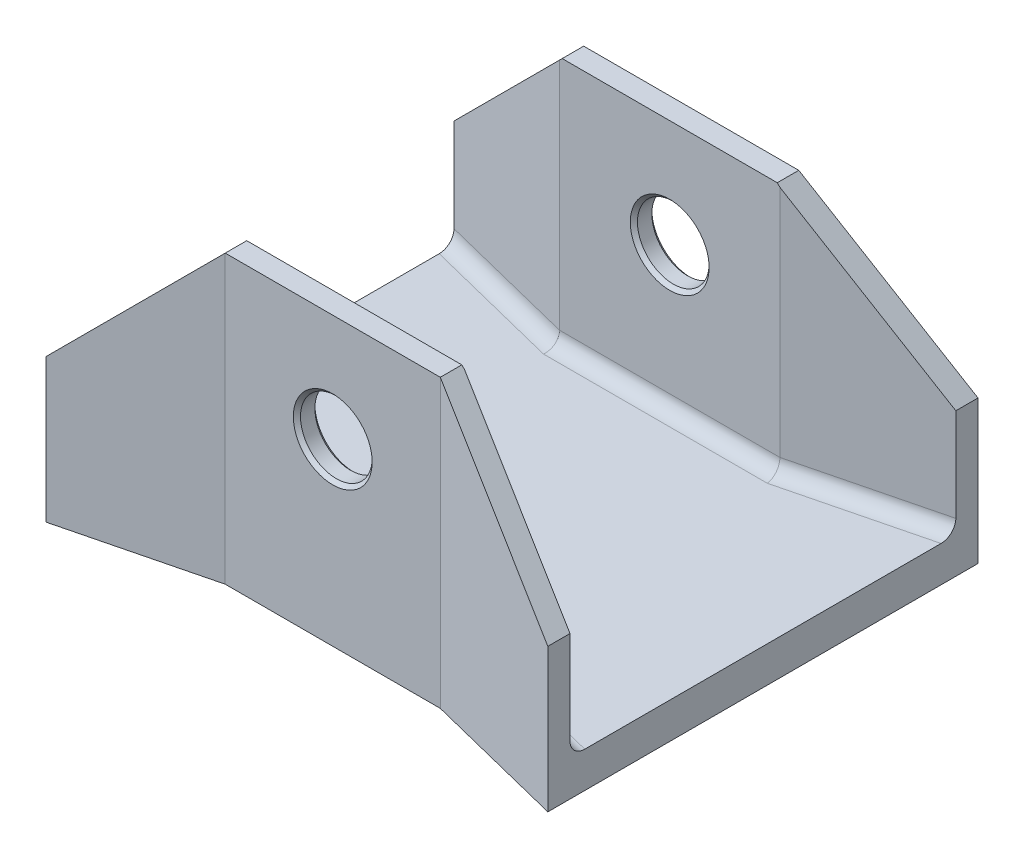
SolidWorks part; units mm, degrees
ref_plane "Front Plane" through (0, 0, 0) normal (0, 0, 1) x (1, 0, 0)
ref_plane "Top Plane" through (0, 0, 0) normal (0, 1, 0) x (1, 0, 0)
ref_plane "Right Plane" through (0, 0, 0) normal (1, 0, 0) x (0, 0, -1)
sketch "Sketch1" plane through (0, 0, 0) normal (0, 1, 0) x (1, 0, 0)
  line L0 (-566.7955, 0) -> (27772.9795, 0) construction
  line L1 (-35, -30) -> (-35, 30)
  line L2 (-35, 30) -> (-15, 25)
  line L3 (-15, 25) -> (15, 25)
  line L4 (0, -566.7955) -> (0, 27772.9795) construction
  line L5 (35, -30) -> (35, 30)
  line L6 (35, 30) -> (15, 25)
  line L7 (35, -30) -> (15, -25)
  line L8 (-15, -25) -> (15, -25)
  line L9 (-35, -30) -> (-15, -25)
  point P1 (0, -25)
  point P6 (0, 10.6994)
  point P10 (0, 25)
  point P15 (35, 0)
  point P17 (-35, 0)
  dimension "D1" = 15
  dimension "D2" = 35
  dimension "D3" = 30
  dimension "D4" = 25
extrude "Boss-Extrude1" add sketch "Sketch1" along normal blind 40
sketch "Sketch2" plane through (0, 40, 0) normal (0, 1, 0) x (1, 0, 0)
  line L0 (-15.3693, 22) -> (-49.9226, 30.6383)
  line L1 (-49.9226, 30.6383) -> (-49.9226, -30.6383)
  line L2 (-49.9226, -30.6383) -> (-15.3693, -22)
  line L3 (-15.3693, -22) -> (15.3693, -22)
  line L4 (15.3693, -22) -> (46.2965, -29.7318)
  line L5 (46.2965, -29.7318) -> (46.2965, 29.7318)
  line L6 (46.2965, 29.7318) -> (15.3693, 22)
  line L7 (15.3693, 22) -> (-15.3693, 22)
extrude "Cut-Extrude1" cut sketch "Sketch2" against normal blind 35
chamfer "Chamfer1" distance 20 angle 45 4 edges at (35, 40, 28.4538) (35, 40, -28.4538) (-35, 40, -28.4538) (-35, 40, 28.4538)
sketch "Sketch4" plane through (0, 0, 25) normal (0, 0, 1) x (1, 0, 0)
  line L0 (-15, 40) -> (15, 40) construction
  circle A0 centre (0, 25) radius 5
  dimension "D1" = 15
extrude "Cut-Extrude2" cut sketch "Sketch4" along direction (0, 0, 1) on the side against the normal through all
fillet "Fillet1" radius 2 6 edges at (-25.1847, 5, 24.4538) (0, 5, 22) (25.1847, 5, 24.4538) (25.1847, 5, -24.4538) (0, 5, -22) (-25.1847, 5, -24.4538)
chamfer "Chamfer2" distance 0.5 angle 45 4 edges at (-5, 25, -22) (5, 25, -25) (5, 25, 22) (5, 25, 25)
